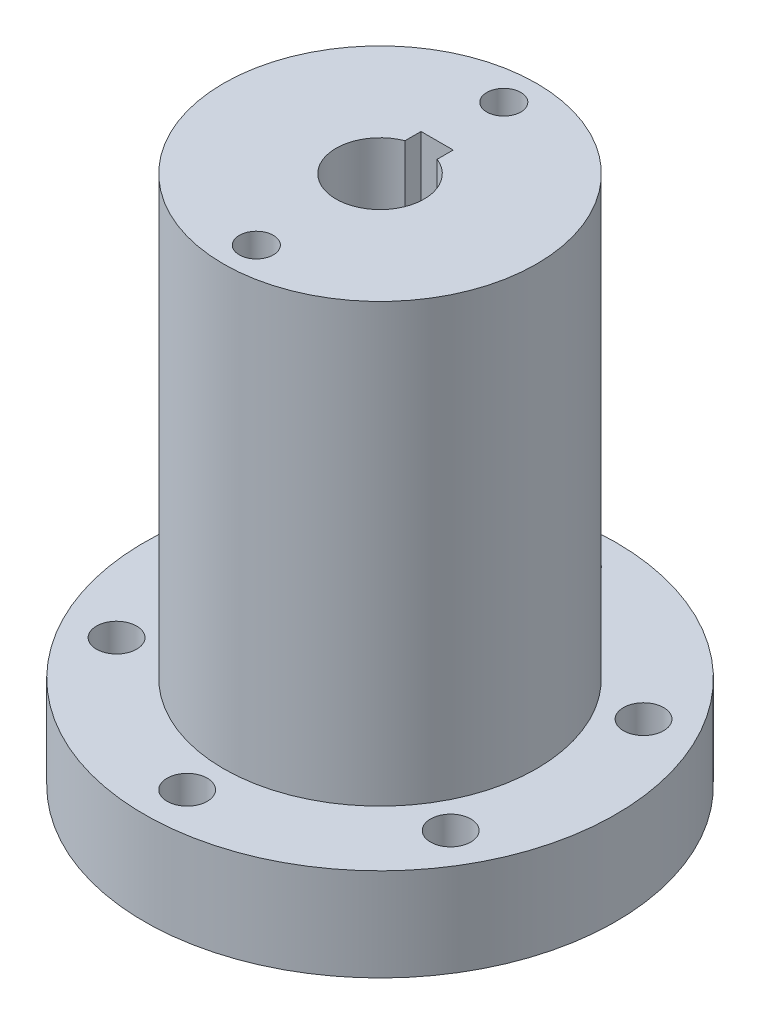
SolidWorks part; units mm, degrees
ref_plane "Front Plane" through (0, 0, 0) normal (0, 0, 1) x (1, 0, 0)
ref_plane "Top Plane" through (0, 0, 0) normal (0, 1, 0) x (1, 0, 0)
ref_plane "Right Plane" through (0, 0, 0) normal (1, 0, 0) x (0, 0, -1)
sketch "Sketch1" plane through (0, 0, 0) normal (0, 1, 0) x (1, 0, 0)
  circle A0 centre (0, 0) radius 25.3
extrude "Boss-Extrude1" add sketch "Sketch1" along normal blind 8.5
sketch "Sketch2" plane through (0, 8.5, 0) normal (0, 1, 0) x (1, 0, 0)
  circle A0 centre (0, 0) radius 25.3
extrude "Boss-Extrude2" add sketch "Sketch2" along normal blind 57.15
sketch "Sketch7" plane through (0, 65.65, 0) normal (0, 1, 0) x (1, 0, 0)
  circle A0 centre (0, 0) radius 25.3
extrude "Boss-Extrude4" add sketch "Sketch7" along normal blind 15
sketch "Sketch5" plane through (0, 0, 0) normal (0, -1, 0) x (1, 0, 0)
  line L1 (-2.575, 9.15) -> (2.575, 9.15)
  line L2 (-2.575, 9.15) -> (-2.575, 4)
  line L3 (-2.575, 4) -> (2.575, 4)
  line L4 (2.575, 9.15) -> (2.575, 4)
  circle A0 centre (0, 0) radius 7.25
  dimension "D1" = 5.15
  dimension "D2" = 5.15
  dimension "D3" = 9.15
  dimension "D4" = 2.575
extrude "Cut-Extrude3" cut sketch "Sketch5" against normal blind 115 contours L2 A0 L4 L3 | L4 A0 L2 L3 | A0 L4 L1 L2 region at (0, 0, 8.1175) region at (0, 0, 5.5505) region at (0, 0, -0.5929)
sketch "Sketch6" plane through (0, 0, 0) normal (0, -1, 0) x (1, 0, 0)
  circle A0 centre (0, 0) radius 38.1
extrude "Boss-Extrude3" add sketch "Sketch6" along normal blind 15
sketch "Sketch9" plane through (0, 0, 0) normal (0, 1, 0) x (1, 0, 0)
  line L1 (0, 31.1769) -> (-27, 15.5885)
  line L2 (-27, 15.5885) -> (-27, -15.5885)
  line L3 (-27, -15.5885) -> (0, -31.1769)
  line L4 (0, -31.1769) -> (27, -15.5885)
  line L5 (27, -15.5885) -> (27, 15.5885)
  line L6 (27, 15.5885) -> (0, 31.1769)
  circle A0 centre (0, 0) radius 27 construction
  circle A1 centre (0, 31.1769) radius 3.25
  circle A2 centre (-27, 15.5885) radius 3.25
  circle A3 centre (-27, -15.5885) radius 3.25
  circle A4 centre (0, -31.1769) radius 3.25
  circle A5 centre (27, -15.5885) radius 3.25
  circle A6 centre (27, 15.5885) radius 3.25
extrude "Cut-Extrude4" cut sketch "Sketch9" against normal blind 20 contours L1 A2 L2 | L2 A2 L1 | L6 A1 L1 | L1 A1 L6 | L5 A6 L6 | L6 A6 L5 | L4 A5 L5 | L5 A5 L4 | L3 A4 L4 | L4 A4 L3 | L2 A3 L3 | L3 A3 L2 region at (0, 0, -29.3851) region at (0, 0, -32.0728) region at (-25.4482, 0, -14.6925) region at (-27.7759, 0, -16.0364) region at (27.7759, 0, -16.0364) region at (25.4482, 0, -14.6925) region at (-25.4482, 0, 14.6925) region at (-27.7759, 0, 16.0364) region at (27.7759, 0, 16.0364) region at (25.4482, 0, 14.6925) region at (0, 0, 29.3851) region at (0, 0, 32.0728)
sketch "Sketch10" plane through (0, 80.65, 0) normal (0, 1, 0) x (1, 0, 0)
  circle A0 centre (0, 20) radius 2.75
  circle A1 centre (0, -20) radius 2.75
  arc A2 (2.575, -6.7773) -> (-2.575, -6.7773) centre (0, 0) ccw construction
  dimension "D1" = 20
  dimension "D2" = 20
extrude "Cut-Extrude6" cut sketch "Sketch10" against normal blind 129
sketch "Sketch11" plane through (0, 80.65, 0) normal (0, 1, 0) x (1, 0, 0)
  line L1 (-2.575, -9.15) -> (2.575, -9.15)
  line L3 (0, -7.12) -> (0, -9.15)
  circle A0 centre (0, 0) radius 7.12
  arc M3 (-2.575, -6.7773) -> (2.575, -6.7773) centre (0, 0) cw
  line M4 (2.575, -6.7773) -> (2.575, -9.15)
  line M5 (2.575, -9.15) -> (-2.575, -9.15)
  line M6 (-2.575, -9.15) -> (-2.575, -6.7773)
  dimension "D1" = 14.24
extrude "Boss-Extrude5" add sketch "Sketch11" against normal blind 93 contours A0 M3 | A0 M6 M5 M4 region at (0, 80.65, 0) region at (-2.3561, 80.65, 7.9637)
sketch "Sketch12" plane through (0, 80.65, 0) normal (0, 1, 0) x (1, 0, 0)
  circle A0 centre (0, 0) radius 25.3
extrude "Cut-Extrude8" cut sketch "Sketch12" against normal blind 10
sketch "Sketch13" plane through (0, 70.65, 0) normal (0, 1, 0) x (1, 0, 0)
  line L0 (0, 7.12) -> (0, 9.22)
  line L1 (0, 9.22) -> (2.6, 9.22)
  line L2 (0, 9.22) -> (-2.6, 9.22)
  line L3 (-2.6, 9.22) -> (-2.6, 6.6283)
  line L4 (2.6, 9.22) -> (2.6, 6.6283)
  circle A0 centre (0, 0) radius 7.12
extrude "Cut-Extrude9" cut sketch "Sketch13" against normal blind 30 contours A0 | A0 L0 L2 L3 | A0 L4 L1 L0 region at (-1.3468, 70.65, -8.0845) region at (1.3468, 70.65, -8.0845) region at (0, 70.65, 0)
